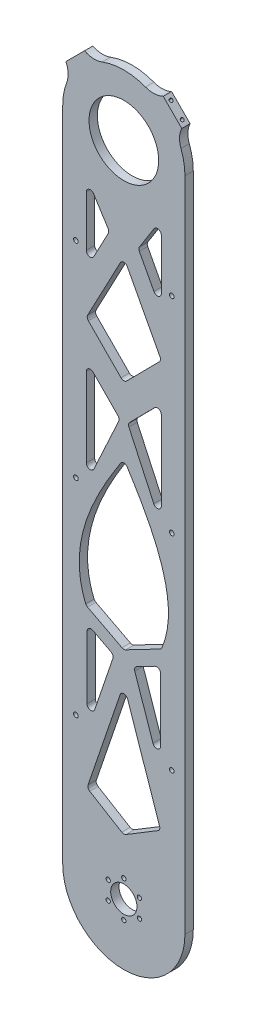
SolidWorks part; units mm, degrees
material "1060 Alloy"
ref_plane "Front Plane" through (0, 0, 0) normal (0, 0, 1) x (1, 0, 0)
ref_plane "Top Plane" through (0, 0, 0) normal (0, 1, 0) x (1, 0, 0)
ref_plane "Right Plane" through (0, 0, 0) normal (1, 0, 0) x (0, 0, -1)
sketch "Sketch2" plane through (0, 0, 0) normal (0, 0, 1) x (1, 0, 0)
  line L0 (0, 0) -> (0, 500) construction
  line L1 (-46.5, 0) -> (-46.5, 500)
  line L2 (46.5, 0) -> (46.5, 500)
  arc A0 (-46.5, 0) -> (46.5, 0) centre (0, 0) ccw
  arc A1 (46.5, 500) -> (-46.5, 500) centre (0, 500) ccw
  circle A2 centre (0, 500) radius 37.25 construction
  circle A3 centre (0, 0) radius 10
  circle A4 centre (0, 13.75) radius 1.65
  circle A5 centre (0, 0) radius 13.75 construction
  circle A6 centre (11.9078, 6.875) radius 1.65
  circle A7 centre (11.9078, -6.875) radius 1.65
  circle A8 centre (0, -13.75) radius 1.65
  circle A9 centre (-11.9078, -6.875) radius 1.65
  circle A10 centre (-11.9078, 6.875) radius 1.65
  point P3 (0, 250)
  point P27 (0, 0)
  dimension "D2" = 74.5
  dimension "D4" = 20
  dimension "D5" = 3.3
  dimension "D6" = 27.5
  dimension "D3" = 46.5
  dimension "D1" = 500
  dimension "D7" = 6
extrude "Boss-Extrude1" add sketch "Sketch2" along normal blind 6.35
sketch "Sketch4" plane through (0, 0, 6.35) normal (0, 0, 1) x (1, 0, 0)
  line L0 (0, 500) -> (0, 999.1647) construction
  line L29 (46.5, 500) -> (-46.5, 500) construction
  line L31 (28.0053, 59.376) -> (0, 42.4117)
  line L32 (0, 141.6934) -> (28.0053, 59.376)
  line L33 (-28.0053, 59.376) -> (0, 141.6934)
  line L34 (0, 42.4117) -> (-28.0053, 59.376)
  line L35 (-7.5, 156.9059) -> (-28.0053, 96.6336)
  line L36 (-28.0053, 167.5829) -> (-7.5, 156.9059)
  line L37 (-28.0053, 96.6336) -> (-28.0053, 167.5829)
  line L38 (28.0053, 167.5829) -> (7.5, 156.9059)
  line L39 (28.0053, 96.6336) -> (28.0053, 167.5829)
  line L40 (7.5, 156.9059) -> (28.0053, 96.6336)
  line L41 (0, 164.2751) -> (28.5505, 179.1412)
  line L42 (0, 164.2751) -> (-28.5505, 179.1412)
  line L43 (28.5505, 259.5868) -> (3, 314.9383)
  line L44 (28.5505, 340.7931) -> (28.5505, 259.5868)
  line L45 (3, 314.9383) -> (28.5505, 340.7931)
  line L46 (-3, 314.9383) -> (-28.5505, 340.7931)
  line L47 (-28.5505, 259.5868) -> (-3, 314.9383)
  line L48 (-28.5505, 340.7931) -> (-28.5505, 259.5868)
  line L49 (0, 423.1428) -> (-28.5505, 369.2462)
  line L50 (-28.5505, 369.2462) -> (0, 340.3557)
  line L51 (0, 340.3557) -> (28.5505, 369.2462)
  line L52 (0, 423.1428) -> (28.5505, 369.2462)
  line L53 (-28.5505, 462.0952) -> (-28.5505, 401.2902)
  line L54 (-11, 434.4215) -> (-28.5505, 462.0952)
  line L55 (-28.5505, 401.2902) -> (-11, 434.4215)
  line L56 (28.5505, 401.2902) -> (11, 434.4215)
  line L57 (28.5505, 462.0952) -> (28.5505, 401.2902)
  line L58 (11, 434.4215) -> (28.5505, 462.0952)
  arc A0 (46.5, 500) -> (-46.5, 500) centre (0, 500) ccw construction
  arc A1 (46.5, 500) -> (-46.5, 500) centre (0, 500) ccw construction
  spline S2 degree 3 poles (28.5505, 179.1412) (45.3203, 216.9857) (19.4301, 259.7903) (0, 290.0258) knots 0 0 0 0 1 1 1 1
  spline S3 degree 3 poles (-28.5505, 179.1412) (-45.3203, 216.9857) (-19.4301, 259.7903) (0, 290.0258) knots 0 0 0 0 1 1 1 1
extrude "Cut-Extrude1" cut sketch "Sketch4" against normal blind 10
fillet "Fillet3" radius 3 30 edges at (-11, 434.4215, 3.175) (-28.5505, 401.2902, 3.175) (28.5505, 401.2902, 3.175) (11, 434.4215, 3.175) (28.5505, 462.0952, 3.175) (-28.5505, 462.0952, 3.175) (0, 423.1428, 3.175) (-28.5505, 369.2462, 3.175) (28.5505, 369.2462, 3.175) (0, 340.3557, 3.175) (28.5505, 340.7931, 3.175) (-28.5505, 340.7931, 3.175) (-3, 314.9383, 3.175) (3, 314.9383, 3.175) (28.5505, 259.5868, 3.175) (-28.5505, 259.5868, 3.175) (28.5505, 179.1412, 3.175) (0, 290.0258, 3.175) (-28.5505, 179.1412, 3.175) (0, 164.2751, 3.175) (-28.0053, 96.6336, 3.175) (28.0053, 96.6336, 3.175) (7.5, 156.9059, 3.175) (-28.0053, 167.5829, 3.175) (28.0053, 167.5829, 3.175) (0, 141.6934, 3.175) (28.0053, 59.376, 3.175) (-28.0053, 59.376, 3.175) (0, 42.4117, 3.175) (-7.5, 156.9059, 3.175)
sketch "Sketch5" plane through (0, 0, 6.35) normal (0, 0, 1) x (1, 0, 0)
  line L0 (0, -46.5) -> (108.8395, -46.5) construction
  line L1 (46.5, 100) -> (-46.5, 100) construction
  line L2 (46.5, 0) -> (46.5, 500) construction
  line L3 (-46.5, 500) -> (-46.5, 0) construction
  line L4 (-46.5, 106.35) -> (46.5, 106.35) construction
  line L5 (36.5, 106.35) -> (36.5, 100) construction
  line L6 (0, 106.35) -> (0, 100) construction
  line L7 (-46.5, 256.35) -> (46.5, 256.35) construction
  line L8 (-46.5, 181.35) -> (46.5, 181.35) construction
  line L9 (-46.5, 337.7) -> (46.5, 337.7) construction
  arc A1 (-46.5, 0) -> (46.5, 0) centre (0, 0) ccw construction
  circle A2 centre (36.5, 103.175) radius 1.75
  circle A3 centre (-36.5, 103.175) radius 1.75
  circle A4 centre (36.5, 259.525) radius 1.75
  circle A5 centre (-36.5, 259.525) radius 1.75
  circle A6 centre (36.5, 415.875) radius 1.75
  circle A7 centre (-36.5, 415.875) radius 1.75
  point P18 (36.5, 103.175)
  dimension "D2" = 3.5
  dimension "D1" = 146.5
  dimension "D3" = 10
  dimension "D4" = 6.35
  dimension "D5" = 150
  dimension "D6" = 81.35
  dimension "D7" = 81.35
extrude "Cut-Extrude2" cut sketch "Sketch5" against normal through all
sketch "Sketch6" plane through (0, 0, 6.35) normal (0, 0, 1) x (1, 0, 0)
  circle A0 centre (0, 500) radius 26.5
  arc A1 (46.5, 500) -> (-46.5, 500) centre (0, 500) ccw construction
  arc A2 (46.5, 500) -> (-46.5, 500) centre (0, 500) ccw construction
  dimension "D1" = 20
extrude "Cut-Extrude3" cut sketch "Sketch6" against normal blind 10
sketch "Sketch7" plane through (0, 0, 6.35) normal (0, 0, 1) x (1, 0, 0)
  line L1 (40.0163, 523.6842) -> (44.1104, 529.9682) construction
  line L2 (23.6842, 540.0163) -> (29.9682, 544.1104) construction
  line L3 (44.1104, 529.9682) -> (29.9682, 544.1104)
  line L4 (0, 500) -> (37.0393, 537.0393) construction
  line L5 (0, 500) -> (0, 546.5) construction
  arc A0 (46.5, 500) -> (-46.5, 500) centre (0, 500) ccw construction
  arc A1 (29.9682, 544.1104) -> (16.4747, 543.4837) centre (22.4977, 559.381) cw
  arc A2 (44.1104, 529.9682) -> (43.4837, 516.4747) centre (59.381, 522.4977) ccw
  arc A3 (16.4747, 543.4837) -> (43.4837, 516.4747) centre (0, 500) cw
  dimension "D3" = 17
  dimension "D5" = 17
  dimension "D1" = 20
  dimension "D2" = 7.5
  dimension "D4" = 8
  dimension "D6" = 8
  dimension "D7" = 45
extrude "Boss-Extrude2" add sketch "Sketch7" against normal up to surface (6.35 mm away) up to face at (26.5, 500, 0)
sketch "Sketch8" plane through (287.0393, 287.0393, 0) normal (0.7071, 0.7071, 0) x (0, 0, -1)
  line L0 (0, 363.5534) -> (-6.35, 363.5534) construction
  line L1 (0, 343.5534) -> (-6.35, 343.5534) construction
  line L2 (-6.35, 343.5534) -> (-6.35, 363.5534) construction
  point P0 (-3.175, 359.5534)
  point P1 (-3.175, 347.5534)
  dimension "D1" = 4
  dimension "D2" = 4
  dimension "D3" = 3.175
hole_wizard "Tap Drill for M3x0.5 Tap1" positions "Sketch8" profile "Sketch9" hole size "M3x0.5" standard "ANSI Metric"
sketch "Sketch9" plane through (32.7967, 541.282, 3.175) normal (0, 0, 1) x (-0.7071, 0.7071, 0)
  line L0 (0, 0) -> (0, 5.7511)
  line L1 (0, 5.7511) -> (1.25, 5)
  line L2 (1.25, 5) -> (1.25, 0)
  line L5 (1.25, 0) -> (0, 0)
  line L10 (0, 5.7511) -> (-1.25, 5) construction
  line L11 (0, -6.35) -> (0, 107.95) construction
  dimension "Hole Dia." = 2.5
  dimension "Hole Depth" = 5
  dimension "Drill Angle" = 118
pattern_circular "CirPattern2" count 2 every 90 about axis through (0, 500, -3.65) along (0, 0, 1) of "Boss-Extrude2", "Tap Drill for M3x0.5 Tap1"
equation "\"L1L\"=500"
equation "\"L1Thick\"=6.35"
equation "\"D1@Sketch2\"=\"L1L\""
equation "\"Harm-Drive-Outer\"=74.5"
equation "\"D2@Sketch2\"=\"Harm-Drive-Outer\""
equation "\"D1@Boss-Extrude1\"=\"L1Thick\""
